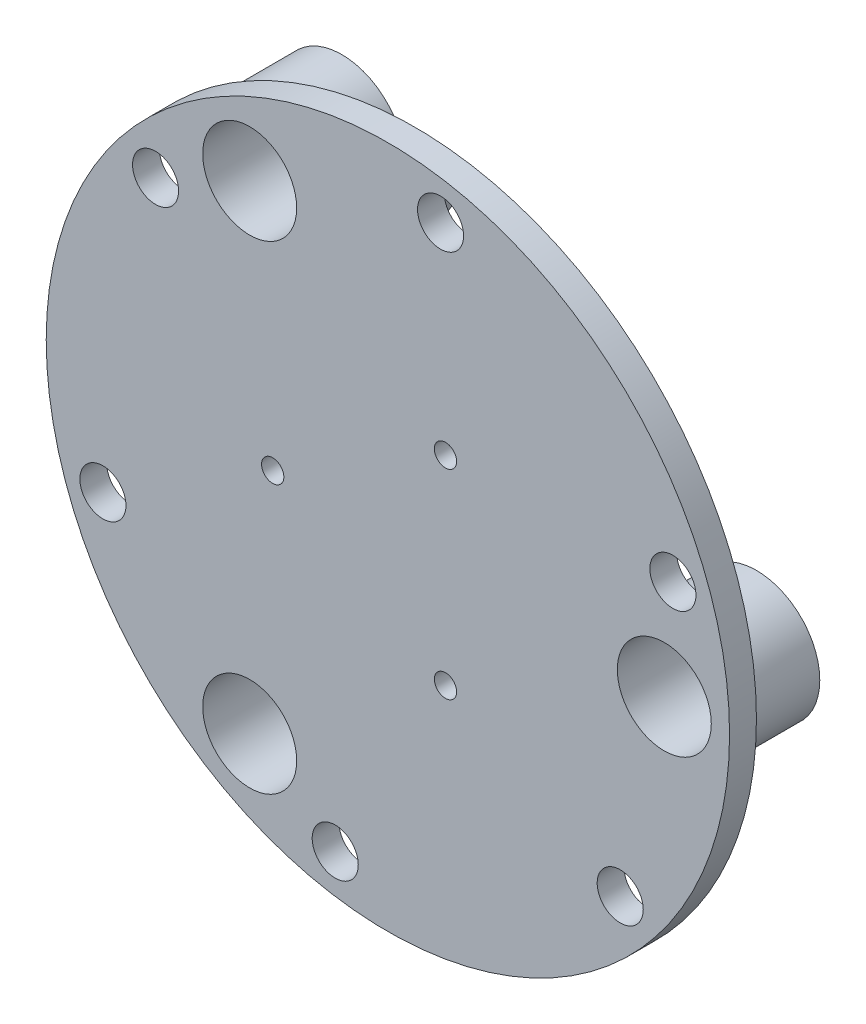
SolidWorks part; units mm, degrees
ref_plane "Front Plane" through (0, 0, 0) normal (0, 0, 1) x (1, 0, 0)
ref_plane "Top Plane" through (0, 0, 0) normal (0, 1, 0) x (1, 0, 0)
ref_plane "Right Plane" through (0, 0, 0) normal (1, 0, 0) x (0, 0, -1)
sketch "S01 - Joining centre of floating Y" plane through (0, 0, 0) normal (0, 0, 1) x (1, 0, 0)
  circle A0 centre (0, 0) radius 9
  dimension "D1" = 18
extrude "01 - Joining centre of floating Y" add sketch "S01 - Joining centre of floating Y" along normal blind 3.5 from offset 33.5
sketch "S02 - Floating spoke 1" plane through (0, 0, 0) normal (0, 0, 1) x (1, 0, 0)
  line L0 (4.65, -8.054) -> (-21.3308, -23.054)
  line L1 (-30.6308, -6.946) -> (-4.65, 8.054)
  arc A0 (-21.3308, -23.054) -> (-30.6308, -6.946) centre (-25.9808, -15) cw
  arc A1 (-4.65, 8.054) -> (4.65, -8.054) centre (0, 0) cw
  dimension "D1" = 9.3
  dimension "D2" = 9.3
  dimension "D3" = 4.65
  dimension "D4" = 4.65
  dimension "D5" = 21.3308
  dimension "D6" = 25.9808
  dimension "D7" = 30.6308
  dimension "D8" = 6.946
extrude "02 - Floating spoke 1" add sketch "S02 - Floating spoke 1" along normal blind 3.5 from offset 33.5
sketch "S03 - Floating spoke 2" plane through (0, 0, 0) normal (0, 0, 1) x (1, 0, 0)
  line L0 (4.65, 8.054) -> (30.6308, -6.946)
  line L1 (21.3308, -23.054) -> (-4.65, -8.054)
  arc A0 (30.6308, -6.946) -> (21.3308, -23.054) centre (25.9808, -15) cw
  arc A1 (-4.65, -8.054) -> (4.65, 8.054) centre (0, 0) cw
  dimension "D1" = 9.3
  dimension "D2" = 9.3
  dimension "D3" = 4.65
  dimension "D4" = 21.3308
  dimension "D5" = 25.9808
  dimension "D6" = 30.6308
  dimension "D7" = 4.65
  dimension "D8" = 6.946
extrude "03 - Floating spoke 2" add sketch "S03 - Floating spoke 2" along normal blind 3.5 from offset 33.5
sketch "S04 - Floating spoke 3" plane through (0, 0, 0) normal (0, 0, 1) x (1, 0, 0)
  line L0 (-9.3, 0) -> (-9.3, 30)
  line L1 (9.3, 30) -> (9.3, 0)
  arc A0 (-9.3, 30) -> (9.3, 30) centre (0, 30) cw
  arc A1 (9.3, 0) -> (-9.3, 0) centre (0, 0) cw
  dimension "D1" = 9.3
  dimension "D2" = 30
extrude "04 - Floating spoke 3" add sketch "S04 - Floating spoke 3" along normal blind 3.5 from offset 33.5
sketch "S05 - Moving tendon tie web 1" plane through (0, 0, 0) normal (0, 0, 1) x (1, 0, 0)
  line L0 (25.2997, -21.2631) -> (6.8189, -19.2535)
  line L1 (8.1811, -6.7273) -> (26.6618, -8.7369)
  arc A0 (6.8189, -19.2535) -> (8.1811, -6.7273) centre (7.5, -12.9904) cw
  arc A1 (26.6618, -8.7369) -> (25.2997, -21.2631) centre (25.9808, -15) cw
  dimension "D1" = 6.3
  dimension "D2" = 6.3
  dimension "D3" = 6.8189
  dimension "D4" = 7.5
  dimension "D5" = 8.1811
  dimension "D6" = 25.2997
  dimension "D7" = 25.9808
  dimension "D8" = 26.6618
  dimension "D9" = 6.7273
  dimension "D10" = 8.7369
extrude "05 - Moving tendon tie web 1" add sketch "S05 - Moving tendon tie web 1" along normal blind 3.5 from offset 33.5
sketch "S06 - Tendon anchor base 1" plane through (0, 0, 0) normal (0, 0, 1) x (1, 0, 0)
  circle A0 centre (7.5, -12.9904) radius 4.2
  dimension "D1" = 8.4
  dimension "D2" = 7.5
  dimension "D3" = 12.9904
extrude "06 - Tendon anchor base 1" add sketch "S06 - Tendon anchor base 1" along normal blind 3.7 from offset 29.8
sketch "S07 - Tendon mouth 1" plane through (0, 0, 0) normal (0, 0, 1) x (1, 0, 0)
  circle A0 centre (7.5, -12.9904) radius 3.15
  dimension "D1" = 6.3
  dimension "D2" = 7.5
  dimension "D3" = 12.9904
extrude "07 - Tendon mouth 1" add sketch "S07 - Tendon mouth 1" along normal blind 1.8 from offset 28
sketch "S08 - Moving tendon tie web 2" plane through (0, 0, 0) normal (0, 0, 1) x (1, 0, 0)
  line L0 (5.7645, 32.5417) -> (13.2645, 15.5321)
  line L1 (1.7355, 10.4487) -> (-5.7645, 27.4583)
  arc A0 (13.2645, 15.5321) -> (1.7355, 10.4487) centre (7.5, 12.9904) cw
  arc A1 (-5.7645, 27.4583) -> (5.7645, 32.5417) centre (0, 30) cw
  dimension "D1" = 6.3
  dimension "D2" = 6.3
  dimension "D3" = 1.7355
  dimension "D4" = 5.7645
  dimension "D5" = 7.5
  dimension "D6" = 13.2645
  dimension "D7" = 5.7645
  dimension "D8" = 10.4487
  dimension "D9" = 27.4583
extrude "08 - Moving tendon tie web 2" add sketch "S08 - Moving tendon tie web 2" along normal blind 3.5 from offset 33.5
sketch "S09 - Tendon anchor base 2" plane through (0, 0, 0) normal (0, 0, 1) x (1, 0, 0)
  circle A0 centre (7.5, 12.9904) radius 4.2
  dimension "D1" = 8.4
  dimension "D2" = 7.5
  dimension "D3" = 12.9904
extrude "09 - Tendon anchor base 2" add sketch "S09 - Tendon anchor base 2" along normal blind 3.7 from offset 29.8
sketch "S10 - Tendon mouth 2" plane through (0, 0, 0) normal (0, 0, 1) x (1, 0, 0)
  circle A0 centre (7.5, 12.9904) radius 3.15
  dimension "D1" = 6.3
  dimension "D2" = 7.5
  dimension "D3" = 12.9904
extrude "10 - Tendon mouth 2" add sketch "S10 - Tendon mouth 2" along normal blind 1.8 from offset 28
sketch "S11 - Moving tendon tie web 3" plane through (0, 0, 0) normal (0, 0, 1) x (1, 0, 0)
  line L0 (-31.0642, -11.2786) -> (-20.0835, 3.7214)
  line L1 (-9.9165, -3.7214) -> (-20.8973, -18.7214)
  arc A0 (-20.0835, 3.7214) -> (-9.9165, -3.7214) centre (-15, 0) cw
  arc A1 (-20.8973, -18.7214) -> (-31.0642, -11.2786) centre (-25.9808, -15) cw
  dimension "D1" = 6.3
  dimension "D2" = 6.3
  dimension "D3" = 9.9165
  dimension "D4" = 15
  dimension "D5" = 20.0835
  dimension "D6" = 20.8973
  dimension "D7" = 25.9808
  dimension "D8" = 31.0642
  dimension "D9" = 11.2786
extrude "11 - Moving tendon tie web 3" add sketch "S11 - Moving tendon tie web 3" along normal blind 3.5 from offset 33.5
sketch "S12 - Tendon anchor base 3" plane through (0, 0, 0) normal (0, 0, 1) x (1, 0, 0)
  circle A0 centre (-15, 0) radius 4.2
  dimension "D1" = 8.4
  dimension "D2" = 15
extrude "12 - Tendon anchor base 3" add sketch "S12 - Tendon anchor base 3" along normal blind 3.7 from offset 29.8
sketch "S13 - Tendon mouth 3" plane through (0, 0, 0) normal (0, 0, 1) x (1, 0, 0)
  circle A0 centre (-15, 0) radius 3.15
  dimension "D1" = 6.3
  dimension "D2" = 15
extrude "13 - Tendon mouth 3" add sketch "S13 - Tendon mouth 3" along normal blind 1.8 from offset 28
sketch "S14 - Joined drive hoop" plane through (0, 0, 0) normal (0, 0, 1) x (1, 0, 0)
  circle A0 centre (0, 0) radius 44.5
  dimension "D2" = 89
extrude "14 - Joined drive hoop" add sketch "S14 - Joined drive hoop" along normal blind 3.5 from offset 33.5
sketch "S15 - Sliding guide barrel 1" plane through (0, 0, 0) normal (0, 0, 1) x (1, 0, 0)
  circle A0 centre (36, 0) radius 8.25
  dimension "D1" = 16.5
  dimension "D2" = 36
extrude "15 - Sliding guide barrel 1" add sketch "S15 - Sliding guide barrel 1" along normal blind 12 from offset 25
sketch "S16 - Sliding guide barrel 2" plane through (0, 0, 0) normal (0, 0, 1) x (1, 0, 0)
  circle A0 centre (-18, 31.1769) radius 8.25
  dimension "D1" = 16.5
  dimension "D2" = 18
  dimension "D3" = 31.1769
extrude "16 - Sliding guide barrel 2" add sketch "S16 - Sliding guide barrel 2" along normal blind 12 from offset 25
sketch "S17 - Sliding guide barrel 3" plane through (0, 0, 0) normal (0, 0, 1) x (1, 0, 0)
  circle A0 centre (-18, -31.1769) radius 8.25
  dimension "D1" = 16.5
  dimension "D2" = 18
  dimension "D3" = 31.1769
extrude "17 - Sliding guide barrel 3" add sketch "S17 - Sliding guide barrel 3" along normal blind 12 from offset 25
sketch "S18 - Guide bushing seats" plane through (0, 0, 0) normal (0, 0, 1) x (1, 0, 0)
  circle A0 centre (36, 0) radius 6.12
  circle A1 centre (-18, 31.1769) radius 6.12
  circle A2 centre (-18, -31.1769) radius 6.12
  dimension "D1" = 12.24
  dimension "D2" = 12.24
  dimension "D3" = 12.24
  dimension "D4" = 36
  dimension "D5" = 18
  dimension "D6" = 31.1769
  dimension "D7" = 31.1769
extrude "18 - Guide bushing seats" cut sketch "S18 - Guide bushing seats" along normal blind 14 from offset 24
sketch "S19 - Through tendon tie eyes" plane through (0, 0, 0) normal (0, 0, 1) x (1, 0, 0)
  circle A0 centre (7.5, -12.9904) radius 1.45
  circle A1 centre (7.5, 12.9904) radius 1.45
  circle A2 centre (-15, 0) radius 1.45
  dimension "D1" = 2.9
  dimension "D2" = 2.9
  dimension "D3" = 2.9
  dimension "D4" = 7.5
  dimension "D5" = 15
  dimension "D6" = 12.9904
  dimension "D7" = 12.9904
extrude "19 - Through tendon tie eyes" cut sketch "S19 - Through tendon tie eyes" along normal blind 10 from offset 27.8
sketch3d "Plane points - Integral B1 fork cheek L"
  point P0 (-25.9808, -15, 28)
  point P1 (-8.5941, -10.3413, 28)
  point P2 (-25.9808, -15, 10)
ref_plane "Drilling plane - Integral B1 fork cheek L" through (2.0096, -7.5, 0) normal (-0.2588, 0.9659, 0) x (0.9659, 0.2588, 0)
sketch "S20 - Integral B1 fork cheek L" plane through (2.0096, -7.5, 0) normal (-0.2588, 0.9659, 0) x (0.9659, 0.2588, 0)
  line L0 (-35.0778, -34.5) -> (-22.8778, -34.5)
  line L1 (-22.8778, -34.5) -> (-24.0278, -28)
  line L2 (-33.9278, -28) -> (-35.0778, -34.5)
  arc A0 (-24.0278, -28) -> (-33.9278, -28) centre (-28.9778, -28) ccw
  dimension "D1" = 4.95
  dimension "D2" = 22.8778
  dimension "D3" = 28.9778
  dimension "D4" = 35.0778
  dimension "D5" = 28
  dimension "D6" = 34.5
extrude "20 - Integral B1 fork cheek L" add sketch "S20 - Integral B1 fork cheek L" along normal blind 3.6 from offset 7.2 offset against normal yes
sketch3d "Plane points - Integral B1 fork cheek R"
  point P0 (-25.9808, -15, 28)
  point P1 (-8.5941, -10.3413, 28)
  point P2 (-25.9808, -15, 10)
ref_plane "Drilling plane - Integral B1 fork cheek R" through (2.0096, -7.5, 0) normal (-0.2588, 0.9659, 0) x (0.9659, 0.2588, 0)
sketch "S21 - Integral B1 fork cheek R" plane through (2.0096, -7.5, 0) normal (-0.2588, 0.9659, 0) x (0.9659, 0.2588, 0)
  line L0 (-35.0778, -34.5) -> (-22.8778, -34.5)
  line L1 (-22.8778, -34.5) -> (-24.0278, -28)
  line L2 (-33.9278, -28) -> (-35.0778, -34.5)
  arc A0 (-24.0278, -28) -> (-33.9278, -28) centre (-28.9778, -28) ccw
  dimension "D1" = 4.95
  dimension "D2" = 22.8778
  dimension "D3" = 28.9778
  dimension "D4" = 35.0778
  dimension "D5" = 28
  dimension "D6" = 34.5
extrude "21 - Integral B1 fork cheek R" add sketch "S21 - Integral B1 fork cheek R" along normal blind 3.6 from offset 3.6
sketch3d "Plane points - B1 pivot through both cheeks"
  point P0 (-25.9808, -15, 28)
  point P1 (-8.5941, -10.3413, 28)
  point P2 (-25.9808, -15, 10)
ref_plane "Drilling plane - B1 pivot through both cheeks" through (2.0096, -7.5, 0) normal (-0.2588, 0.9659, 0) x (0.9659, 0.2588, 0)
sketch "S22 - B1 pivot through both cheeks" plane through (2.0096, -7.5, 0) normal (-0.2588, 0.9659, 0) x (0.9659, 0.2588, 0)
  circle A0 centre (-28.9778, -28) radius 1.65
  dimension "D1" = 3.3
  dimension "D2" = 28.9778
  dimension "D3" = 28
extrude "22 - B1 pivot through both cheeks" cut sketch "S22 - B1 pivot through both cheeks" along normal blind 15 from offset 7.5 offset against normal yes
sketch3d "Plane points - B1 recessed pivot screw head"
  point P0 (-25.9808, -15, 28)
  point P1 (-8.5941, -10.3413, 28)
  point P2 (-25.9808, -15, 10)
ref_plane "Drilling plane - B1 recessed pivot screw head" through (2.0096, -7.5, 0) normal (-0.2588, 0.9659, 0) x (0.9659, 0.2588, 0)
sketch "S23 - B1 recessed pivot screw head" plane through (2.0096, -7.5, 0) normal (-0.2588, 0.9659, 0) x (0.9659, 0.2588, 0)
  circle A0 centre (-28.9778, -28) radius 2.7
  dimension "D1" = 5.4
  dimension "D2" = 28.9778
  dimension "D3" = 28
extrude "23 - B1 recessed pivot screw head" cut sketch "S23 - B1 recessed pivot screw head" along normal blind 1.5 from offset 7.3 offset against normal yes
sketch3d "Plane points - Integral B2 fork cheek L"
  point P0 (25.9808, -15, 28)
  point P1 (13.2528, -2.2721, 28)
  point P2 (25.9808, -15, 10)
ref_plane "Drilling plane - Integral B2 fork cheek L" through (5.4904, 5.4904, 0) normal (-0.7071, -0.7071, 0) x (0, 0, 1)
sketch "S24 - Integral B2 fork cheek L" plane through (5.4904, 5.4904, 0) normal (-0.7071, -0.7071, 0) x (0, 0, 1)
  line L0 (34.5, -35.0778) -> (34.5, -22.8778)
  line L1 (34.5, -22.8778) -> (28, -24.0278)
  line L2 (28, -33.9278) -> (34.5, -35.0778)
  arc A0 (28, -24.0278) -> (28, -33.9278) centre (28, -28.9778) ccw
  dimension "D1" = 4.95
  dimension "D2" = 28
  dimension "D3" = 34.5
  dimension "D4" = 22.8778
  dimension "D5" = 28.9778
  dimension "D6" = 35.0778
extrude "24 - Integral B2 fork cheek L" add sketch "S24 - Integral B2 fork cheek L" along normal blind 3.6 from offset 7.2 offset against normal yes
sketch3d "Plane points - Integral B2 fork cheek R"
  point P0 (25.9808, -15, 28)
  point P1 (13.2528, -2.2721, 28)
  point P2 (25.9808, -15, 10)
ref_plane "Drilling plane - Integral B2 fork cheek R" through (5.4904, 5.4904, 0) normal (-0.7071, -0.7071, 0) x (0, 0, 1)
sketch "S25 - Integral B2 fork cheek R" plane through (5.4904, 5.4904, 0) normal (-0.7071, -0.7071, 0) x (0, 0, 1)
  line L0 (34.5, -35.0778) -> (34.5, -22.8778)
  line L1 (34.5, -22.8778) -> (28, -24.0278)
  line L2 (28, -33.9278) -> (34.5, -35.0778)
  arc A0 (28, -24.0278) -> (28, -33.9278) centre (28, -28.9778) ccw
  dimension "D1" = 4.95
  dimension "D2" = 28
  dimension "D3" = 34.5
  dimension "D4" = 22.8778
  dimension "D5" = 28.9778
  dimension "D6" = 35.0778
extrude "25 - Integral B2 fork cheek R" add sketch "S25 - Integral B2 fork cheek R" along normal blind 3.6 from offset 3.6
sketch3d "Plane points - B2 pivot through both cheeks"
  point P0 (25.9808, -15, 28)
  point P1 (13.2528, -2.2721, 28)
  point P2 (25.9808, -15, 10)
ref_plane "Drilling plane - B2 pivot through both cheeks" through (5.4904, 5.4904, 0) normal (-0.7071, -0.7071, 0) x (0, 0, 1)
sketch "S26 - B2 pivot through both cheeks" plane through (5.4904, 5.4904, 0) normal (-0.7071, -0.7071, 0) x (0, 0, 1)
  circle A0 centre (28, -28.9778) radius 2.6
  dimension "D1" = 5.2
  dimension "D2" = 28
  dimension "D3" = 28.9778
extrude "26 - B2 pivot through both cheeks" cut sketch "S26 - B2 pivot through both cheeks" along normal blind 15 from offset 7.5 offset against normal yes
sketch3d "Plane points - B2 recessed pivot screw head"
  point P0 (25.9808, -15, 28)
  point P1 (13.2528, -2.2721, 28)
  point P2 (25.9808, -15, 10)
ref_plane "Drilling plane - B2 recessed pivot screw head" through (5.4904, 5.4904, 0) normal (-0.7071, -0.7071, 0) x (0, 0, 1)
sketch "S27 - B2 recessed pivot screw head" plane through (5.4904, 5.4904, 0) normal (-0.7071, -0.7071, 0) x (0, 0, 1)
  circle A0 centre (28, -28.9778) radius 2.7
  dimension "D1" = 5.4
  dimension "D2" = 28
  dimension "D3" = 28.9778
extrude "27 - B2 recessed pivot screw head" cut sketch "S27 - B2 recessed pivot screw head" along normal blind 1.5 from offset 7.3 offset against normal yes
sketch3d "Plane points - Integral B3 fork cheek L"
  point P0 (0, 30, 28)
  point P1 (-4.6587, 12.6133, 28)
  point P2 (0, 30, 10)
ref_plane "Drilling plane - Integral B3 fork cheek L" through (-7.5, 2.0096, 0) normal (0.9659, -0.2588, 0) x (0, 0, -1)
sketch "S28 - Integral B3 fork cheek L" plane through (-7.5, 2.0096, 0) normal (0.9659, -0.2588, 0) x (0, 0, -1)
  line L0 (-34.5, 35.0778) -> (-34.5, 22.8778)
  line L1 (-34.5, 22.8778) -> (-28, 24.0278)
  line L2 (-28, 33.9278) -> (-34.5, 35.0778)
  arc A0 (-28, 24.0278) -> (-28, 33.9278) centre (-28, 28.9778) ccw
  dimension "D1" = 4.95
  dimension "D2" = 28
  dimension "D3" = 34.5
  dimension "D4" = 22.8778
  dimension "D5" = 28.9778
  dimension "D6" = 35.0778
extrude "28 - Integral B3 fork cheek L" add sketch "S28 - Integral B3 fork cheek L" along normal blind 3.6 from offset 7.2 offset against normal yes
sketch3d "Plane points - Integral B3 fork cheek R"
  point P0 (0, 30, 28)
  point P1 (-4.6587, 12.6133, 28)
  point P2 (0, 30, 10)
ref_plane "Drilling plane - Integral B3 fork cheek R" through (-7.5, 2.0096, 0) normal (0.9659, -0.2588, 0) x (0, 0, -1)
sketch "S29 - Integral B3 fork cheek R" plane through (-7.5, 2.0096, 0) normal (0.9659, -0.2588, 0) x (0, 0, -1)
  line L0 (-34.5, 35.0778) -> (-34.5, 22.8778)
  line L1 (-34.5, 22.8778) -> (-28, 24.0278)
  line L2 (-28, 33.9278) -> (-34.5, 35.0778)
  arc A0 (-28, 24.0278) -> (-28, 33.9278) centre (-28, 28.9778) ccw
  dimension "D1" = 4.95
  dimension "D2" = 28
  dimension "D3" = 34.5
  dimension "D4" = 22.8778
  dimension "D5" = 28.9778
  dimension "D6" = 35.0778
extrude "29 - Integral B3 fork cheek R" add sketch "S29 - Integral B3 fork cheek R" along normal blind 3.6 from offset 3.6
sketch3d "Plane points - B3 pivot through both cheeks"
  point P0 (0, 30, 28)
  point P1 (-4.6587, 12.6133, 28)
  point P2 (0, 30, 10)
ref_plane "Drilling plane - B3 pivot through both cheeks" through (-7.5, 2.0096, 0) normal (0.9659, -0.2588, 0) x (0, 0, -1)
sketch "S30 - B3 pivot through both cheeks" plane through (-7.5, 2.0096, 0) normal (0.9659, -0.2588, 0) x (0, 0, -1)
  circle A0 centre (-28, 28.9778) radius 2.6
  dimension "D1" = 5.2
  dimension "D2" = 28
  dimension "D3" = 28.9778
extrude "30 - B3 pivot through both cheeks" cut sketch "S30 - B3 pivot through both cheeks" along normal blind 15 from offset 7.5 offset against normal yes
sketch3d "Plane points - B3 recessed pivot screw head"
  point P0 (0, 30, 28)
  point P1 (-4.6587, 12.6133, 28)
  point P2 (0, 30, 10)
ref_plane "Drilling plane - B3 recessed pivot screw head" through (-7.5, 2.0096, 0) normal (0.9659, -0.2588, 0) x (0, 0, -1)
sketch "S31 - B3 recessed pivot screw head" plane through (-7.5, 2.0096, 0) normal (0.9659, -0.2588, 0) x (0, 0, -1)
  circle A0 centre (-28, 28.9778) radius 2.7
  dimension "D1" = 5.4
  dimension "D2" = 28
  dimension "D3" = 28.9778
extrude "31 - B3 recessed pivot screw head" cut sketch "S31 - B3 recessed pivot screw head" along normal blind 1.5 from offset 7.3 offset against normal yes
sketch "Sketch1" plane through (0.1461, -0.5453, 0) normal (-0.2588, 0.9659, 0) x (0.9659, 0.2588, 0)
  circle A0 centre (-28.9778, -28) radius 2.6
  dimension "D1" = 5.2
extrude "Cut-Extrude1" cut sketch "Sketch1" against normal blind 16 and the other way through all
other "Fork inner faces - 8.40 mm lug clearance" flip direction yes face at (-27.5604, -19.1503, 28) face at (-29.4239, -12.1956, 28) face at (30.3648, -14.2929, 28) face at (25.2737, -19.3841, 28) face at (-2.8044, 33.4432, 28) face at (4.1503, 31.5797, 28) offset 0.6 parameters "D1"=0.6
ref_plane "Guide saddle feet" through (0, 0, 25.5) normal (0, 0, 1) x (1, 0, 0)
ref_plane "Guide saddle roots" through (0, 0, 33.6) normal (0, 0, 1) x (1, 0, 0)
sketch "Barrel 1 saddle foot" plane through (0, 0, 25.5) normal (0, 0, 1) x (1, 0, 0)
  line L0 (36, -8) -> (31, -8)
  line L1 (31, -8) -> (27, -3)
  line L2 (27, 3) -> (31, 8)
  line L3 (31, 8) -> (36, 8)
  line L4 (36, 8) -> (36, 7)
  line L5 (36, -7) -> (36, -8)
  arc A0 (27, -3) -> (27, 3) centre (27, 0) cw
  arc A1 (36, 7) -> (36, -7) centre (36, 0) ccw
sketch "Barrel 1 saddle root" plane through (0, 0, 33.6) normal (0, 0, 1) x (1, 0, 0)
  line L0 (36, -8) -> (31, -8)
  line L1 (31, -8) -> (20, -4)
  line L2 (20, 4) -> (31, 8)
  line L3 (31, 8) -> (36, 8)
  line L4 (36, 8) -> (36, 7)
  line L5 (36, -7) -> (36, -8)
  arc A0 (20, -4) -> (20, 4) centre (20, 0) cw
  arc A1 (36, 7) -> (36, -7) centre (36, 0) ccw
loft "Guide barrel 1 - tapered wraparound saddle" [suppressed] add profiles "Barrel 1 saddle foot", "Barrel 1 saddle root"
sketch "Barrel 2 saddle foot" plane through (0, 0, 25.5) normal (0, 0, 1) x (1, 0, 0)
  line L0 (-11.0718, 35.1769) -> (-8.5718, 30.8468)
  line L1 (-8.5718, 30.8468) -> (-10.9019, 24.8827)
  line L2 (-16.0981, 21.8827) -> (-22.4282, 22.8468)
  line L3 (-22.4282, 22.8468) -> (-24.9282, 27.1769)
  line L4 (-24.9282, 27.1769) -> (-24.0622, 27.6769)
  line L5 (-11.9378, 34.6769) -> (-11.0718, 35.1769)
  arc A0 (-10.9019, 24.8827) -> (-16.0981, 21.8827) centre (-13.5, 23.3827) cw
  arc A1 (-24.0622, 27.6769) -> (-11.9378, 34.6769) centre (-18, 31.1769) ccw
sketch "Barrel 2 saddle root" plane through (0, 0, 33.6) normal (0, 0, 1) x (1, 0, 0)
  line L0 (-11.0718, 35.1769) -> (-8.5718, 30.8468)
  line L1 (-8.5718, 30.8468) -> (-6.5359, 19.3205)
  line L2 (-13.4641, 15.3205) -> (-22.4282, 22.8468)
  line L3 (-22.4282, 22.8468) -> (-24.9282, 27.1769)
  line L4 (-24.9282, 27.1769) -> (-24.0622, 27.6769)
  line L5 (-11.9378, 34.6769) -> (-11.0718, 35.1769)
  arc A0 (-6.5359, 19.3205) -> (-13.4641, 15.3205) centre (-10, 17.3205) cw
  arc A1 (-24.0622, 27.6769) -> (-11.9378, 34.6769) centre (-18, 31.1769) ccw
loft "Guide barrel 2 - tapered wraparound saddle" [suppressed] add profiles "Barrel 2 saddle foot", "Barrel 2 saddle root"
sketch "Barrel 3 saddle foot" plane through (0, 0, 25.5) normal (0, 0, 1) x (1, 0, 0)
  line L0 (-24.9282, -27.1769) -> (-22.4282, -22.8468)
  line L1 (-22.4282, -22.8468) -> (-16.0981, -21.8827)
  line L2 (-10.9019, -24.8827) -> (-8.5718, -30.8468)
  line L3 (-8.5718, -30.8468) -> (-11.0718, -35.1769)
  line L4 (-11.0718, -35.1769) -> (-11.9378, -34.6769)
  line L5 (-24.0622, -27.6769) -> (-24.9282, -27.1769)
  arc A0 (-16.0981, -21.8827) -> (-10.9019, -24.8827) centre (-13.5, -23.3827) cw
  arc A1 (-11.9378, -34.6769) -> (-24.0622, -27.6769) centre (-18, -31.1769) ccw
sketch "Barrel 3 saddle root" plane through (0, 0, 33.6) normal (0, 0, 1) x (1, 0, 0)
  line L0 (-24.9282, -27.1769) -> (-22.4282, -22.8468)
  line L1 (-22.4282, -22.8468) -> (-13.4641, -15.3205)
  line L2 (-6.5359, -19.3205) -> (-8.5718, -30.8468)
  line L3 (-8.5718, -30.8468) -> (-11.0718, -35.1769)
  line L4 (-11.0718, -35.1769) -> (-11.9378, -34.6769)
  line L5 (-24.0622, -27.6769) -> (-24.9282, -27.1769)
  arc A0 (-13.4641, -15.3205) -> (-6.5359, -19.3205) centre (-10, -17.3205) cw
  arc A1 (-11.9378, -34.6769) -> (-24.0622, -27.6769) centre (-18, -31.1769) ccw
loft "Guide barrel 3 - tapered wraparound saddle" [suppressed] add profiles "Barrel 3 saddle foot", "Barrel 3 saddle root"
sketch "Tangent R6.5 transitions at guide stations" plane through (0, 0, 0) normal (0, 0, 1) x (1, 0, 0)
  line L0 (39.3501, -7.5392) -> (35.4, -7.5)
  line L1 (35.4, -7.5) -> (35.8006, -11.4924)
  line L2 (39.3501, 7.5392) -> (35.4, 7.5)
  line L3 (35.4, 7.5) -> (35.8006, 11.4924)
  line L4 (-13.1459, 37.8478) -> (-11.2048, 34.4073)
  line L5 (-11.2048, 34.4073) -> (-7.9476, 36.7505)
  line L6 (-26.2042, 30.3086) -> (-24.1952, 26.9073)
  line L7 (-24.1952, 26.9073) -> (-27.853, 25.258)
  line L8 (-26.2042, -30.3086) -> (-24.1952, -26.9073)
  line L9 (-24.1952, -26.9073) -> (-27.853, -25.258)
  line L10 (-13.1459, -37.8478) -> (-11.2048, -34.4073)
  line L11 (-11.2048, -34.4073) -> (-7.9476, -36.7505)
  arc A0 (35.8006, -11.4924) -> (39.3501, -7.5392) centre (41.9895, -13.4792) cw
  arc A1 (35.8006, 11.4924) -> (39.3501, 7.5392) centre (41.9895, 13.4792) ccw
  arc A2 (-7.9476, 36.7505) -> (-13.1459, 37.8478) centre (-9.3215, 43.1036) cw
  arc A3 (-27.853, 25.258) -> (-26.2042, 30.3086) centre (-32.6681, 29.6244) ccw
  arc A4 (-27.853, -25.258) -> (-26.2042, -30.3086) centre (-32.6681, -29.6244) cw
  arc A5 (-7.9476, -36.7505) -> (-13.1459, -37.8478) centre (-9.3215, -43.1036) ccw
extrude "Continuous deck rim around bearing housings" [suppressed] add sketch "Tangent R6.5 transitions at guide stations" along normal blind 3.5 from offset 33.5
sketch3d "Guide 1 clockwise anchor section"
  line L0 (11.4747, -15.0801, 33.56) -> (8.53, -8.6195, 33.56)
  line L1 (8.53, -8.6195, 33.56) -> (8.9447, -9.5295, 32.56)
  line L2 (8.9447, -9.5295, 32.56) -> (9.1313, -9.939, 30.55)
  line L3 (9.1313, -9.939, 30.55) -> (9.318, -10.3484, 30.1)
  line L4 (9.318, -10.3484, 30.1) -> (10.6867, -13.3512, 30.1)
  line L5 (10.6867, -13.3512, 30.1) -> (10.8733, -13.7607, 30.55)
  line L6 (10.8733, -13.7607, 30.55) -> (11.0599, -14.1702, 32.56)
  line L7 (11.0599, -14.1702, 32.56) -> (11.4747, -15.0801, 33.56)
sketch3d "Guide 1 clockwise web section"
  line L0 (19.1463, -10.8141, 33.56) -> (16.7822, -5.6274, 33.56)
  line L1 (16.7822, -5.6274, 33.56) -> (17.197, -6.5374, 32.56)
  line L2 (17.197, -6.5374, 32.56) -> (17.3836, -6.9468, 30.45)
  line L3 (17.3836, -6.9468, 30.45) -> (17.5702, -7.3563, 30)
  line L4 (17.5702, -7.3563, 30) -> (18.3583, -9.0852, 30)
  line L5 (18.3583, -9.0852, 30) -> (18.5449, -9.4947, 30.45)
  line L6 (18.5449, -9.4947, 30.45) -> (18.7315, -9.9041, 32.56)
  line L7 (18.7315, -9.9041, 32.56) -> (19.1463, -10.8141, 33.56)
sketch3d "Guide 1 clockwise haunch section"
  line L0 (26.5692, -7.7604, 33.56) -> (23.9563, -2.0278, 33.56)
  line L1 (23.9563, -2.0278, 33.56) -> (24.3711, -2.9377, 32.56)
  line L2 (24.3711, -2.9377, 32.56) -> (24.5577, -3.3472, 27.45)
  line L3 (24.5577, -3.3472, 27.45) -> (24.7443, -3.7566, 27)
  line L4 (24.7443, -3.7566, 27) -> (25.7812, -6.0315, 27)
  line L5 (25.7812, -6.0315, 27) -> (25.9678, -6.441, 27.45)
  line L6 (25.9678, -6.441, 27.45) -> (26.1545, -6.8504, 32.56)
  line L7 (26.1545, -6.8504, 32.56) -> (26.5692, -7.7604, 33.56)
sketch3d "Guide 1 clockwise housing section"
  line L0 (31.8441, -6.6748, 33.56) -> (28.2358, 1.2416, 33.56)
  line L1 (28.2358, 1.2416, 33.56) -> (28.6505, 0.3317, 32.56)
  line L2 (28.6505, 0.3317, 32.56) -> (28.8371, -0.0778, 25.9)
  line L3 (28.8371, -0.0778, 25.9) -> (29.0238, -0.4873, 25.45)
  line L4 (29.0238, -0.4873, 25.45) -> (31.0561, -4.946, 25.45)
  line L5 (31.0561, -4.946, 25.45) -> (31.2427, -5.3554, 25.9)
  line L6 (31.2427, -5.3554, 25.9) -> (31.4293, -5.7649, 32.56)
  line L7 (31.4293, -5.7649, 32.56) -> (31.8441, -6.6748, 33.56)
loft "Guide 1 clockwise bearing-to-anchor rib" [suppressed] add profiles "Guide 1 clockwise anchor section", "Guide 1 clockwise web section", "Guide 1 clockwise haunch section", "Guide 1 clockwise housing section"
sketch3d "Guide 1 counterclockwise anchor section"
  line L0 (8.53, 8.6195, 33.56) -> (11.4747, 15.0801, 33.56)
  line L1 (11.4747, 15.0801, 33.56) -> (11.0599, 14.1702, 32.56)
  line L2 (11.0599, 14.1702, 32.56) -> (10.8733, 13.7607, 30.55)
  line L3 (10.8733, 13.7607, 30.55) -> (10.6867, 13.3512, 30.1)
  line L4 (10.6867, 13.3512, 30.1) -> (9.318, 10.3484, 30.1)
  line L5 (9.318, 10.3484, 30.1) -> (9.1313, 9.939, 30.55)
  line L6 (9.1313, 9.939, 30.55) -> (8.9447, 9.5295, 32.56)
  line L7 (8.9447, 9.5295, 32.56) -> (8.53, 8.6195, 33.56)
sketch3d "Guide 1 counterclockwise web section"
  line L0 (16.7822, 5.6274, 33.56) -> (19.1463, 10.8141, 33.56)
  line L1 (19.1463, 10.8141, 33.56) -> (18.7315, 9.9041, 32.56)
  line L2 (18.7315, 9.9041, 32.56) -> (18.5449, 9.4947, 30.45)
  line L3 (18.5449, 9.4947, 30.45) -> (18.3583, 9.0852, 30)
  line L4 (18.3583, 9.0852, 30) -> (17.5702, 7.3563, 30)
  line L5 (17.5702, 7.3563, 30) -> (17.3836, 6.9468, 30.45)
  line L6 (17.3836, 6.9468, 30.45) -> (17.197, 6.5374, 32.56)
  line L7 (17.197, 6.5374, 32.56) -> (16.7822, 5.6274, 33.56)
sketch3d "Guide 1 counterclockwise haunch section"
  line L0 (23.9563, 2.0278, 33.56) -> (26.5692, 7.7604, 33.56)
  line L1 (26.5692, 7.7604, 33.56) -> (26.1545, 6.8504, 32.56)
  line L2 (26.1545, 6.8504, 32.56) -> (25.9678, 6.441, 27.45)
  line L3 (25.9678, 6.441, 27.45) -> (25.7812, 6.0315, 27)
  line L4 (25.7812, 6.0315, 27) -> (24.7443, 3.7566, 27)
  line L5 (24.7443, 3.7566, 27) -> (24.5577, 3.3472, 27.45)
  line L6 (24.5577, 3.3472, 27.45) -> (24.3711, 2.9377, 32.56)
  line L7 (24.3711, 2.9377, 32.56) -> (23.9563, 2.0278, 33.56)
sketch3d "Guide 1 counterclockwise housing section"
  line L0 (28.2358, -1.2416, 33.56) -> (31.8441, 6.6748, 33.56)
  line L1 (31.8441, 6.6748, 33.56) -> (31.4293, 5.7649, 32.56)
  line L2 (31.4293, 5.7649, 32.56) -> (31.2427, 5.3554, 25.9)
  line L3 (31.2427, 5.3554, 25.9) -> (31.0561, 4.946, 25.45)
  line L4 (31.0561, 4.946, 25.45) -> (29.0238, 0.4873, 25.45)
  line L5 (29.0238, 0.4873, 25.45) -> (28.8371, 0.0778, 25.9)
  line L6 (28.8371, 0.0778, 25.9) -> (28.6505, -0.3317, 32.56)
  line L7 (28.6505, -0.3317, 32.56) -> (28.2358, -1.2416, 33.56)
loft "Guide 1 counterclockwise bearing-to-anchor rib" [suppressed] add profiles "Guide 1 counterclockwise anchor section", "Guide 1 counterclockwise web section", "Guide 1 counterclockwise haunch section", "Guide 1 counterclockwise housing section"
sketch3d "Guide 2 clockwise anchor section"
  line L0 (7.3224, 17.4774, 33.56) -> (3.1998, 11.6969, 33.56)
  line L1 (3.1998, 11.6969, 33.56) -> (3.7804, 12.5111, 32.56)
  line L2 (3.7804, 12.5111, 32.56) -> (4.0417, 12.8775, 30.55)
  line L3 (4.0417, 12.8775, 30.55) -> (4.303, 13.2438, 30.1)
  line L4 (4.303, 13.2438, 30.1) -> (6.2192, 15.9305, 30.1)
  line L5 (6.2192, 15.9305, 30.1) -> (6.4804, 16.2969, 30.55)
  line L6 (6.4804, 16.2969, 30.55) -> (6.7417, 16.6633, 32.56)
  line L7 (6.7417, 16.6633, 32.56) -> (7.3224, 17.4774, 33.56)
sketch3d "Guide 2 clockwise web section"
  line L0 (-0.2079, 21.9882, 33.56) -> (-3.5176, 17.3475, 33.56)
  line L1 (-3.5176, 17.3475, 33.56) -> (-2.937, 18.1617, 32.56)
  line L2 (-2.937, 18.1617, 32.56) -> (-2.6757, 18.5281, 30.45)
  line L3 (-2.6757, 18.5281, 30.45) -> (-2.4144, 18.8944, 30)
  line L4 (-2.4144, 18.8944, 30) -> (-1.3111, 20.4413, 30)
  line L5 (-1.3111, 20.4413, 30) -> (-1.0498, 20.8077, 30.45)
  line L6 (-1.0498, 20.8077, 30.45) -> (-0.7885, 21.1741, 32.56)
  line L7 (-0.7885, 21.1741, 32.56) -> (-0.2079, 21.9882, 33.56)
sketch3d "Guide 2 clockwise haunch section"
  line L0 (-6.564, 26.8898, 33.56) -> (-10.2221, 21.7606, 33.56)
  line L1 (-10.2221, 21.7606, 33.56) -> (-9.6414, 22.5748, 32.56)
  line L2 (-9.6414, 22.5748, 32.56) -> (-9.3801, 22.9412, 27.45)
  line L3 (-9.3801, 22.9412, 27.45) -> (-9.1188, 23.3075, 27)
  line L4 (-9.1188, 23.3075, 27) -> (-7.6672, 25.3429, 27)
  line L5 (-7.6672, 25.3429, 27) -> (-7.4059, 25.7093, 27.45)
  line L6 (-7.4059, 25.7093, 27.45) -> (-7.1446, 26.0757, 32.56)
  line L7 (-7.1446, 26.0757, 32.56) -> (-6.564, 26.8898, 33.56)
sketch3d "Guide 2 clockwise housing section"
  line L0 (-10.1415, 30.9152, 33.56) -> (-15.1931, 23.8321, 33.56)
  line L1 (-15.1931, 23.8321, 33.56) -> (-14.6125, 24.6462, 32.56)
  line L2 (-14.6125, 24.6462, 32.56) -> (-14.3512, 25.0126, 25.9)
  line L3 (-14.3512, 25.0126, 25.9) -> (-14.0899, 25.379, 25.45)
  line L4 (-14.0899, 25.379, 25.45) -> (-11.2447, 29.3683, 25.45)
  line L5 (-11.2447, 29.3683, 25.45) -> (-10.9834, 29.7347, 25.9)
  line L6 (-10.9834, 29.7347, 25.9) -> (-10.7221, 30.1011, 32.56)
  line L7 (-10.7221, 30.1011, 32.56) -> (-10.1415, 30.9152, 33.56)
loft "Guide 2 clockwise bearing-to-anchor rib" [suppressed] add profiles "Guide 2 clockwise anchor section", "Guide 2 clockwise web section", "Guide 2 clockwise haunch section", "Guide 2 clockwise housing section"
sketch3d "Guide 2 counterclockwise anchor section"
  line L0 (-11.7297, 3.0774, 33.56) -> (-18.7971, 2.3973, 33.56)
  line L1 (-18.7971, 2.3973, 33.56) -> (-17.8017, 2.4931, 32.56)
  line L2 (-17.8017, 2.4931, 32.56) -> (-17.3537, 2.5362, 30.55)
  line L3 (-17.3537, 2.5362, 30.55) -> (-16.9058, 2.5793, 30.1)
  line L4 (-16.9058, 2.5793, 30.1) -> (-13.621, 2.8954, 30.1)
  line L5 (-13.621, 2.8954, 30.1) -> (-13.1731, 2.9385, 30.55)
  line L6 (-13.1731, 2.9385, 30.55) -> (-12.7251, 2.9816, 32.56)
  line L7 (-12.7251, 2.9816, 32.56) -> (-11.7297, 3.0774, 33.56)
sketch3d "Guide 2 counterclockwise web section"
  line L0 (-13.2646, 11.7201, 33.56) -> (-18.9384, 11.1741, 33.56)
  line L1 (-18.9384, 11.1741, 33.56) -> (-17.943, 11.2699, 32.56)
  line L2 (-17.943, 11.2699, 32.56) -> (-17.4951, 11.313, 30.45)
  line L3 (-17.4951, 11.313, 30.45) -> (-17.0471, 11.3561, 30)
  line L4 (-17.0471, 11.3561, 30) -> (-15.1559, 11.5381, 30)
  line L5 (-15.1559, 11.5381, 30) -> (-14.7079, 11.5812, 30.45)
  line L6 (-14.7079, 11.5812, 30.45) -> (-14.26, 11.6243, 32.56)
  line L7 (-14.26, 11.6243, 32.56) -> (-13.2646, 11.7201, 33.56)
sketch3d "Guide 2 counterclockwise haunch section"
  line L0 (-13.7342, 19.7329, 33.56) -> (-20.0053, 19.1295, 33.56)
  line L1 (-20.0053, 19.1295, 33.56) -> (-19.0099, 19.2252, 32.56)
  line L2 (-19.0099, 19.2252, 32.56) -> (-18.5619, 19.2683, 27.45)
  line L3 (-18.5619, 19.2683, 27.45) -> (-18.114, 19.3114, 27)
  line L4 (-18.114, 19.3114, 27) -> (-15.6255, 19.5509, 27)
  line L5 (-15.6255, 19.5509, 27) -> (-15.1776, 19.594, 27.45)
  line L6 (-15.1776, 19.594, 27.45) -> (-14.7297, 19.6371, 32.56)
  line L7 (-14.7297, 19.6371, 32.56) -> (-13.7342, 19.7329, 33.56)
sketch3d "Guide 2 counterclockwise housing section"
  line L0 (-13.0426, 25.0737, 33.56) -> (-21.7026, 24.2404, 33.56)
  line L1 (-21.7026, 24.2404, 33.56) -> (-20.7072, 24.3362, 32.56)
  line L2 (-20.7072, 24.3362, 32.56) -> (-20.2593, 24.3793, 25.9)
  line L3 (-20.2593, 24.3793, 25.9) -> (-19.8114, 24.4224, 25.45)
  line L4 (-19.8114, 24.4224, 25.45) -> (-14.9339, 24.8917, 25.45)
  line L5 (-14.9339, 24.8917, 25.45) -> (-14.486, 24.9348, 25.9)
  line L6 (-14.486, 24.9348, 25.9) -> (-14.038, 24.9779, 32.56)
  line L7 (-14.038, 24.9779, 32.56) -> (-13.0426, 25.0737, 33.56)
loft "Guide 2 counterclockwise bearing-to-anchor rib" [suppressed] add profiles "Guide 2 counterclockwise anchor section", "Guide 2 counterclockwise web section", "Guide 2 counterclockwise haunch section", "Guide 2 counterclockwise housing section"
sketch3d "Guide 3 clockwise anchor section"
  line L0 (-18.7971, -2.3973, 33.56) -> (-11.7297, -3.0774, 33.56)
  line L1 (-11.7297, -3.0774, 33.56) -> (-12.7251, -2.9816, 32.56)
  line L2 (-12.7251, -2.9816, 32.56) -> (-13.1731, -2.9385, 30.55)
  line L3 (-13.1731, -2.9385, 30.55) -> (-13.621, -2.8954, 30.1)
  line L4 (-13.621, -2.8954, 30.1) -> (-16.9058, -2.5793, 30.1)
  line L5 (-16.9058, -2.5793, 30.1) -> (-17.3537, -2.5362, 30.55)
  line L6 (-17.3537, -2.5362, 30.55) -> (-17.8017, -2.4931, 32.56)
  line L7 (-17.8017, -2.4931, 32.56) -> (-18.7971, -2.3973, 33.56)
sketch3d "Guide 3 clockwise web section"
  line L0 (-18.9384, -11.1741, 33.56) -> (-13.2646, -11.7201, 33.56)
  line L1 (-13.2646, -11.7201, 33.56) -> (-14.26, -11.6243, 32.56)
  line L2 (-14.26, -11.6243, 32.56) -> (-14.7079, -11.5812, 30.45)
  line L3 (-14.7079, -11.5812, 30.45) -> (-15.1559, -11.5381, 30)
  line L4 (-15.1559, -11.5381, 30) -> (-17.0471, -11.3561, 30)
  line L5 (-17.0471, -11.3561, 30) -> (-17.4951, -11.313, 30.45)
  line L6 (-17.4951, -11.313, 30.45) -> (-17.943, -11.2699, 32.56)
  line L7 (-17.943, -11.2699, 32.56) -> (-18.9384, -11.1741, 33.56)
sketch3d "Guide 3 clockwise haunch section"
  line L0 (-20.0053, -19.1295, 33.56) -> (-13.7342, -19.7329, 33.56)
  line L1 (-13.7342, -19.7329, 33.56) -> (-14.7297, -19.6371, 32.56)
  line L2 (-14.7297, -19.6371, 32.56) -> (-15.1776, -19.594, 27.45)
  line L3 (-15.1776, -19.594, 27.45) -> (-15.6255, -19.5509, 27)
  line L4 (-15.6255, -19.5509, 27) -> (-18.114, -19.3114, 27)
  line L5 (-18.114, -19.3114, 27) -> (-18.5619, -19.2683, 27.45)
  line L6 (-18.5619, -19.2683, 27.45) -> (-19.0099, -19.2252, 32.56)
  line L7 (-19.0099, -19.2252, 32.56) -> (-20.0053, -19.1295, 33.56)
sketch3d "Guide 3 clockwise housing section"
  line L0 (-21.7026, -24.2404, 33.56) -> (-13.0426, -25.0737, 33.56)
  line L1 (-13.0426, -25.0737, 33.56) -> (-14.038, -24.9779, 32.56)
  line L2 (-14.038, -24.9779, 32.56) -> (-14.486, -24.9348, 25.9)
  line L3 (-14.486, -24.9348, 25.9) -> (-14.9339, -24.8917, 25.45)
  line L4 (-14.9339, -24.8917, 25.45) -> (-19.8114, -24.4224, 25.45)
  line L5 (-19.8114, -24.4224, 25.45) -> (-20.2593, -24.3793, 25.9)
  line L6 (-20.2593, -24.3793, 25.9) -> (-20.7072, -24.3362, 32.56)
  line L7 (-20.7072, -24.3362, 32.56) -> (-21.7026, -24.2404, 33.56)
loft "Guide 3 clockwise bearing-to-anchor rib" [suppressed] add profiles "Guide 3 clockwise anchor section", "Guide 3 clockwise web section", "Guide 3 clockwise haunch section", "Guide 3 clockwise housing section"
sketch3d "Guide 3 counterclockwise anchor section"
  line L0 (3.1998, -11.6969, 33.56) -> (7.3224, -17.4774, 33.56)
  line L1 (7.3224, -17.4774, 33.56) -> (6.7417, -16.6633, 32.56)
  line L2 (6.7417, -16.6633, 32.56) -> (6.4804, -16.2969, 30.55)
  line L3 (6.4804, -16.2969, 30.55) -> (6.2192, -15.9305, 30.1)
  line L4 (6.2192, -15.9305, 30.1) -> (4.303, -13.2438, 30.1)
  line L5 (4.303, -13.2438, 30.1) -> (4.0417, -12.8775, 30.55)
  line L6 (4.0417, -12.8775, 30.55) -> (3.7804, -12.5111, 32.56)
  line L7 (3.7804, -12.5111, 32.56) -> (3.1998, -11.6969, 33.56)
sketch3d "Guide 3 counterclockwise web section"
  line L0 (-3.5176, -17.3475, 33.56) -> (-0.2079, -21.9882, 33.56)
  line L1 (-0.2079, -21.9882, 33.56) -> (-0.7885, -21.1741, 32.56)
  line L2 (-0.7885, -21.1741, 32.56) -> (-1.0498, -20.8077, 30.45)
  line L3 (-1.0498, -20.8077, 30.45) -> (-1.3111, -20.4413, 30)
  line L4 (-1.3111, -20.4413, 30) -> (-2.4144, -18.8944, 30)
  line L5 (-2.4144, -18.8944, 30) -> (-2.6757, -18.5281, 30.45)
  line L6 (-2.6757, -18.5281, 30.45) -> (-2.937, -18.1617, 32.56)
  line L7 (-2.937, -18.1617, 32.56) -> (-3.5176, -17.3475, 33.56)
sketch3d "Guide 3 counterclockwise haunch section"
  line L0 (-10.2221, -21.7606, 33.56) -> (-6.564, -26.8898, 33.56)
  line L1 (-6.564, -26.8898, 33.56) -> (-7.1446, -26.0757, 32.56)
  line L2 (-7.1446, -26.0757, 32.56) -> (-7.4059, -25.7093, 27.45)
  line L3 (-7.4059, -25.7093, 27.45) -> (-7.6672, -25.3429, 27)
  line L4 (-7.6672, -25.3429, 27) -> (-9.1188, -23.3075, 27)
  line L5 (-9.1188, -23.3075, 27) -> (-9.3801, -22.9412, 27.45)
  line L6 (-9.3801, -22.9412, 27.45) -> (-9.6414, -22.5748, 32.56)
  line L7 (-9.6414, -22.5748, 32.56) -> (-10.2221, -21.7606, 33.56)
sketch3d "Guide 3 counterclockwise housing section"
  line L0 (-15.1931, -23.8321, 33.56) -> (-10.1415, -30.9152, 33.56)
  line L1 (-10.1415, -30.9152, 33.56) -> (-10.7221, -30.1011, 32.56)
  line L2 (-10.7221, -30.1011, 32.56) -> (-10.9834, -29.7347, 25.9)
  line L3 (-10.9834, -29.7347, 25.9) -> (-11.2447, -29.3683, 25.45)
  line L4 (-11.2447, -29.3683, 25.45) -> (-14.0899, -25.379, 25.45)
  line L5 (-14.0899, -25.379, 25.45) -> (-14.3512, -25.0126, 25.9)
  line L6 (-14.3512, -25.0126, 25.9) -> (-14.6125, -24.6462, 32.56)
  line L7 (-14.6125, -24.6462, 32.56) -> (-15.1931, -23.8321, 33.56)
loft "Guide 3 counterclockwise bearing-to-anchor rib" [suppressed] add profiles "Guide 3 counterclockwise anchor section", "Guide 3 counterclockwise web section", "Guide 3 counterclockwise haunch section", "Guide 3 counterclockwise housing section"
sketch "Six radiused carrier openings" plane through (0, 0, 0) normal (0, 0, 1) x (1, 0, 0)
  line L0 (13.6035, -5.5701) -> (22.1253, -1.8315)
  line L1 (22.1253, 1.8315) -> (13.6035, 5.5701)
  line L2 (10.8, 3.7386) -> (10.8, -3.7386)
  line L3 (26.2356, 15.0695) -> (25.2894, 19.0749)
  line L4 (23.9074, 20.9252) -> (14.2389, 26.4581)
  line L5 (10.0422, 23.0395) -> (10.902, 20.4109)
  line L6 (11.9821, 18.946) -> (21.737, 12.0363)
  line L7 (-1.9779, 14.566) -> (-9.4765, 20.0768)
  line L8 (-12.6488, 18.2453) -> (-11.6256, 8.9959)
  line L9 (-8.6377, 7.4838) -> (-2.1623, 11.2224)
  line L10 (-26.1683, 15.1859) -> (-29.164, 12.3638)
  line L11 (-30.0755, 10.2418) -> (-30.0328, -0.8978)
  line L12 (-24.9739, -2.8229) -> (-23.1274, -0.764)
  line L13 (-22.3988, 0.9038) -> (-21.2922, 12.8066)
  line L14 (-11.6256, -8.9959) -> (-12.6488, -18.2453)
  line L15 (-9.4765, -20.0768) -> (-1.9779, -14.566)
  line L16 (-2.1623, -11.2224) -> (-8.6377, -7.4838)
  line L17 (-0.0672, -30.2554) -> (3.8747, -31.4387)
  line L18 (6.1681, -31.1671) -> (15.7939, -25.5603)
  line L19 (14.9317, -20.2166) -> (12.2253, -19.6469)
  line L20 (10.4167, -19.8498) -> (-0.4447, -24.8429)
  arc A0 (10.8, -3.7386) -> (13.6035, -5.5701) centre (12.8, -3.7386) ccw
  arc A1 (22.1253, -1.8315) -> (22.1253, 1.8315) centre (21.3218, 0) ccw
  arc A2 (13.6035, 5.5701) -> (10.8, 3.7386) centre (12.8, 3.7386) ccw
  arc A3 (21.737, 12.0363) -> (26.2356, 15.0695) centre (23.4132, 14.4028) ccw
  arc A4 (25.2894, 19.0749) -> (23.9074, 20.9252) centre (22.4671, 18.4082) ccw
  arc A5 (14.2389, 26.4581) -> (10.0422, 23.0395) centre (12.7985, 23.9411) ccw
  arc A6 (10.902, 20.4109) -> (11.9821, 18.946) centre (13.6583, 21.3125) ccw
  arc A7 (-2.1623, 11.2224) -> (-1.9779, 14.566) centre (-3.1623, 12.9544) ccw
  arc A8 (-9.4765, 20.0768) -> (-12.6488, 18.2453) centre (-10.6609, 18.4652) ccw
  arc A9 (-11.6256, 8.9959) -> (-8.6377, 7.4838) centre (-9.6377, 9.2158) ccw
  arc A10 (-21.2922, 12.8066) -> (-26.1683, 15.1859) centre (-24.1798, 13.0751) ccw
  arc A11 (-29.164, 12.3638) -> (-30.0755, 10.2418) centre (-27.1755, 10.2529) ccw
  arc A12 (-30.0328, -0.8978) -> (-24.9739, -2.8229) centre (-27.1328, -0.8867) ccw
  arc A13 (-23.1274, -0.764) -> (-22.3988, 0.9038) centre (-25.2863, 1.1722) ccw
  arc A14 (-8.6377, -7.4838) -> (-11.6256, -8.9959) centre (-9.6377, -9.2158) ccw
  arc A15 (-12.6488, -18.2453) -> (-9.4765, -20.0768) centre (-10.6609, -18.4652) ccw
  arc A16 (-1.9779, -14.566) -> (-2.1623, -11.2224) centre (-3.1623, -12.9544) ccw
  arc A17 (-0.4447, -24.8429) -> (-0.0672, -30.2554) centre (0.7666, -27.4778) ccw
  arc A18 (3.8747, -31.4387) -> (6.1681, -31.1671) centre (4.7084, -28.6612) ccw
  arc A19 (15.7939, -25.5603) -> (14.9317, -20.2166) centre (14.3343, -23.0544) ccw
  arc A20 (12.2253, -19.6469) -> (10.4167, -19.8498) centre (11.628, -22.4847) ccw
extrude "Open deck between guide, tendon and fork stations" [suppressed] cut sketch "Six radiused carrier openings" against normal blind 3.65 from offset 37.05
sketch3d "Guide 1 right trapezoidal rib - tendon end"
  line L0 (10.7863, -13.6904, 33.55) -> (9.1273, -10.0507, 33.55)
  line L1 (9.1273, -10.0507, 33.55) -> (9.2955, -10.4197, 31.25)
  line L2 (9.2955, -10.4197, 31.25) -> (10.6181, -13.3214, 31.25)
  line L3 (10.6181, -13.3214, 31.25) -> (10.7863, -13.6904, 33.55)
sketch3d "Guide 1 right trapezoidal rib - guide end"
  line L0 (31.1932, -5.4879, 33.55) -> (28.7047, -0.0283, 33.55)
  line L1 (28.7047, -0.0283, 33.55) -> (29.1618, -1.0311, 27.3)
  line L2 (29.1618, -1.0311, 27.3) -> (30.7361, -4.4851, 27.3)
  line L3 (30.7361, -4.4851, 27.3) -> (31.1932, -5.4879, 33.55)
loft "Guide 1 right trapezoidal rib" [suppressed] add profiles "Guide 1 right trapezoidal rib - tendon end", "Guide 1 right trapezoidal rib - guide end"
sketch3d "Guide 1 left trapezoidal rib - tendon end"
  line L0 (9.1273, 10.0507, 33.55) -> (10.7863, 13.6904, 33.55)
  line L1 (10.7863, 13.6904, 33.55) -> (10.6181, 13.3214, 31.25)
  line L2 (10.6181, 13.3214, 31.25) -> (9.2955, 10.4197, 31.25)
  line L3 (9.2955, 10.4197, 31.25) -> (9.1273, 10.0507, 33.55)
sketch3d "Guide 1 left trapezoidal rib - guide end"
  line L0 (28.7047, 0.0283, 33.55) -> (31.1932, 5.4879, 33.55)
  line L1 (31.1932, 5.4879, 33.55) -> (30.7361, 4.4851, 27.3)
  line L2 (30.7361, 4.4851, 27.3) -> (29.1618, 1.0311, 27.3)
  line L3 (29.1618, 1.0311, 27.3) -> (28.7047, 0.0283, 33.55)
loft "Guide 1 left trapezoidal rib" [suppressed] add profiles "Guide 1 left trapezoidal rib - tendon end", "Guide 1 left trapezoidal rib - guide end"
sketch3d "Guide 2 right trapezoidal rib - tendon end"
  line L0 (6.4631, 16.1864, 33.55) -> (4.1405, 12.9298, 33.55)
  line L1 (4.1405, 12.9298, 33.55) -> (4.376, 13.26, 31.25)
  line L2 (4.376, 13.26, 31.25) -> (6.2276, 15.8563, 31.25)
  line L3 (6.2276, 15.8563, 31.25) -> (6.4631, 16.1864, 33.55)
sketch3d "Guide 2 right trapezoidal rib - guide end"
  line L0 (-10.8439, 29.758, 33.55) -> (-14.3278, 24.8731, 33.55)
  line L1 (-14.3278, 24.8731, 33.55) -> (-13.6879, 25.7704, 27.3)
  line L2 (-13.6879, 25.7704, 27.3) -> (-11.4838, 28.8608, 27.3)
  line L3 (-11.4838, 28.8608, 27.3) -> (-10.8439, 29.758, 33.55)
loft "Guide 2 right trapezoidal rib" [suppressed] add profiles "Guide 2 right trapezoidal rib - tendon end", "Guide 2 right trapezoidal rib - guide end"
sketch3d "Guide 2 left trapezoidal rib - tendon end"
  line L0 (-13.2678, 2.8792, 33.55) -> (-17.2494, 2.496, 33.55)
  line L1 (-17.2494, 2.496, 33.55) -> (-16.8457, 2.5349, 31.25)
  line L2 (-16.8457, 2.5349, 31.25) -> (-13.6715, 2.8403, 31.25)
  line L3 (-13.6715, 2.8403, 31.25) -> (-13.2678, 2.8792, 33.55)
sketch3d "Guide 2 left trapezoidal rib - guide end"
  line L0 (-14.3768, 24.8448, 33.55) -> (-20.3493, 24.2701, 33.55)
  line L1 (-20.3493, 24.2701, 33.55) -> (-19.2523, 24.3757, 27.3)
  line L2 (-19.2523, 24.3757, 27.3) -> (-15.4738, 24.7393, 27.3)
  line L3 (-15.4738, 24.7393, 27.3) -> (-14.3768, 24.8448, 33.55)
loft "Guide 2 left trapezoidal rib" [suppressed] add profiles "Guide 2 left trapezoidal rib - tendon end", "Guide 2 left trapezoidal rib - guide end"
sketch3d "Guide 3 right trapezoidal rib - tendon end"
  line L0 (-17.2494, -2.496, 33.55) -> (-13.2678, -2.8792, 33.55)
  line L1 (-13.2678, -2.8792, 33.55) -> (-13.6715, -2.8403, 31.25)
  line L2 (-13.6715, -2.8403, 31.25) -> (-16.8457, -2.5349, 31.25)
  line L3 (-16.8457, -2.5349, 31.25) -> (-17.2494, -2.496, 33.55)
sketch3d "Guide 3 right trapezoidal rib - guide end"
  line L0 (-20.3493, -24.2701, 33.55) -> (-14.3768, -24.8448, 33.55)
  line L1 (-14.3768, -24.8448, 33.55) -> (-15.4738, -24.7393, 27.3)
  line L2 (-15.4738, -24.7393, 27.3) -> (-19.2523, -24.3757, 27.3)
  line L3 (-19.2523, -24.3757, 27.3) -> (-20.3493, -24.2701, 33.55)
loft "Guide 3 right trapezoidal rib" [suppressed] add profiles "Guide 3 right trapezoidal rib - tendon end", "Guide 3 right trapezoidal rib - guide end"
sketch3d "Guide 3 left trapezoidal rib - tendon end"
  line L0 (4.1405, -12.9298, 33.55) -> (6.4631, -16.1864, 33.55)
  line L1 (6.4631, -16.1864, 33.55) -> (6.2276, -15.8563, 31.25)
  line L2 (6.2276, -15.8563, 31.25) -> (4.376, -13.26, 31.25)
  line L3 (4.376, -13.26, 31.25) -> (4.1405, -12.9298, 33.55)
sketch3d "Guide 3 left trapezoidal rib - guide end"
  line L0 (-14.3278, -24.8731, 33.55) -> (-10.8439, -29.758, 33.55)
  line L1 (-10.8439, -29.758, 33.55) -> (-11.4838, -28.8608, 27.3)
  line L2 (-11.4838, -28.8608, 27.3) -> (-13.6879, -25.7704, 27.3)
  line L3 (-13.6879, -25.7704, 27.3) -> (-14.3278, -24.8731, 33.55)
loft "Guide 3 left trapezoidal rib" [suppressed] add profiles "Guide 3 left trapezoidal rib - tendon end", "Guide 3 left trapezoidal rib - guide end"
sketch "Six 6 mm holes on 79 mm pitch circle" plane through (0, 0, 0) normal (0, 0, 1) x (1, 0, 0)
  circle A0 centre (37.1179, 13.5098) radius 3
  circle A1 centre (6.8591, 38.8999) radius 3
  circle A2 centre (-30.2588, 25.3901) radius 3
  circle A3 centre (-37.1179, -13.5098) radius 3
  circle A4 centre (-6.8591, -38.8999) radius 3
  circle A5 centre (30.2588, -25.3901) radius 3
  circle A6 centre (0, 0) radius 39.5 construction
extrude "Six lightening holes at 60 degrees" cut sketch "Six 6 mm holes on 79 mm pitch circle" against normal blind 3.7 from offset 37.1
sketch "Central hub - 11 mm across flats" plane through (0, 0, 0) normal (0, 0, 1) x (1, 0, 0)
  line L0 (5.5, 3.1754) -> (0, 6.3509)
  line L1 (0, 6.3509) -> (-5.5, 3.1754)
  line L2 (-5.5, 3.1754) -> (-5.5, -3.1754)
  line L3 (-5.5, -3.1754) -> (0, -6.3509)
  line L4 (0, -6.3509) -> (5.5, -3.1754)
  line L5 (5.5, -3.1754) -> (5.5, 3.1754)
extrude "Central six-sided rib junction" add sketch "Central hub - 11 mm across flats" along normal blind 3 from offset 30.55
sketch3d "Guide 1 radial trapezoidal rib - root"
  line L0 (4.85, -2.25, 33.55) -> (4.85, 2.25, 33.55)
  line L1 (4.85, 2.25, 33.55) -> (4.85, 1.7263, 30.58)
  line L2 (4.85, 1.7263, 30.58) -> (4.85, -1.7263, 30.58)
  line L3 (4.85, -1.7263, 30.58) -> (4.85, -2.25, 33.55)
sketch3d "Guide 1 radial trapezoidal rib - tip"
  line L0 (29.15, -2.7, 33.55) -> (29.15, 2.7, 33.55)
  line L1 (29.15, 2.7, 33.55) -> (29.15, 1.4481, 26.45)
  line L2 (29.15, 1.4481, 26.45) -> (29.15, -1.4481, 26.45)
  line L3 (29.15, -1.4481, 26.45) -> (29.15, -2.7, 33.55)
loft "Guide 1 radial trapezoidal rib" add profiles "Guide 1 radial trapezoidal rib - root", "Guide 1 radial trapezoidal rib - tip"
sketch3d "Tendon 1 radial trapezoidal rib - root"
  line L0 (4.0271, 3.2752, 33.55) -> (0.8229, 5.1252, 33.55)
  line L1 (0.8229, 5.1252, 33.55) -> (1.2764, 4.8634, 30.58)
  line L2 (1.2764, 4.8634, 30.58) -> (3.5736, 3.5371, 30.58)
  line L3 (3.5736, 3.5371, 30.58) -> (4.0271, 3.2752, 33.55)
sketch3d "Tendon 1 radial trapezoidal rib - tip"
  line L0 (7.7704, 9.6588, 33.55) -> (4.4796, 11.5588, 33.55)
  line L1 (4.4796, 11.5588, 33.55) -> (4.9865, 11.2661, 30.23)
  line L2 (4.9865, 11.2661, 30.23) -> (7.2635, 9.9515, 30.23)
  line L3 (7.2635, 9.9515, 30.23) -> (7.7704, 9.6588, 33.55)
loft "Tendon 1 radial trapezoidal rib" add profiles "Tendon 1 radial trapezoidal rib - root", "Tendon 1 radial trapezoidal rib - tip"
sketch3d "Guide 2 radial trapezoidal rib - root"
  line L0 (-0.4764, 5.3252, 33.55) -> (-4.3736, 3.0752, 33.55)
  line L1 (-4.3736, 3.0752, 33.55) -> (-3.92, 3.3371, 30.58)
  line L2 (-3.92, 3.3371, 30.58) -> (-0.93, 5.0634, 30.58)
  line L3 (-0.93, 5.0634, 30.58) -> (-0.4764, 5.3252, 33.55)
sketch3d "Guide 2 radial trapezoidal rib - tip"
  line L0 (-12.2367, 26.5946, 33.55) -> (-16.9133, 23.8946, 33.55)
  line L1 (-16.9133, 23.8946, 33.55) -> (-15.8291, 24.5206, 26.45)
  line L2 (-15.8291, 24.5206, 26.45) -> (-13.3209, 25.9687, 26.45)
  line L3 (-13.3209, 25.9687, 26.45) -> (-12.2367, 26.5946, 33.55)
loft "Guide 2 radial trapezoidal rib" add profiles "Guide 2 radial trapezoidal rib - root", "Guide 2 radial trapezoidal rib - tip"
sketch3d "Tendon 2 radial trapezoidal rib - root"
  line L0 (-4.85, 1.85, 33.55) -> (-4.85, -1.85, 33.55)
  line L1 (-4.85, -1.85, 33.55) -> (-4.85, -1.3263, 30.58)
  line L2 (-4.85, -1.3263, 30.58) -> (-4.85, 1.3263, 30.58)
  line L3 (-4.85, 1.3263, 30.58) -> (-4.85, 1.85, 33.55)
sketch3d "Tendon 2 radial trapezoidal rib - tip"
  line L0 (-12.25, 1.9, 33.55) -> (-12.25, -1.9, 33.55)
  line L1 (-12.25, -1.9, 33.55) -> (-12.25, -1.3146, 30.23)
  line L2 (-12.25, -1.3146, 30.23) -> (-12.25, 1.3146, 30.23)
  line L3 (-12.25, 1.3146, 30.23) -> (-12.25, 1.9, 33.55)
loft "Tendon 2 radial trapezoidal rib" add profiles "Tendon 2 radial trapezoidal rib - root", "Tendon 2 radial trapezoidal rib - tip"
sketch3d "Guide 3 radial trapezoidal rib - root"
  line L0 (-4.3736, -3.0752, 33.55) -> (-0.4764, -5.3252, 33.55)
  line L1 (-0.4764, -5.3252, 33.55) -> (-0.93, -5.0634, 30.58)
  line L2 (-0.93, -5.0634, 30.58) -> (-3.92, -3.3371, 30.58)
  line L3 (-3.92, -3.3371, 30.58) -> (-4.3736, -3.0752, 33.55)
sketch3d "Guide 3 radial trapezoidal rib - tip"
  line L0 (-16.9133, -23.8946, 33.55) -> (-12.2367, -26.5946, 33.55)
  line L1 (-12.2367, -26.5946, 33.55) -> (-13.3209, -25.9687, 26.45)
  line L2 (-13.3209, -25.9687, 26.45) -> (-15.8291, -24.5206, 26.45)
  line L3 (-15.8291, -24.5206, 26.45) -> (-16.9133, -23.8946, 33.55)
loft "Guide 3 radial trapezoidal rib" add profiles "Guide 3 radial trapezoidal rib - root", "Guide 3 radial trapezoidal rib - tip"
sketch3d "Tendon 3 radial trapezoidal rib - root"
  line L0 (0.8229, -5.1252, 33.55) -> (4.0271, -3.2752, 33.55)
  line L1 (4.0271, -3.2752, 33.55) -> (3.5736, -3.5371, 30.58)
  line L2 (3.5736, -3.5371, 30.58) -> (1.2764, -4.8634, 30.58)
  line L3 (1.2764, -4.8634, 30.58) -> (0.8229, -5.1252, 33.55)
sketch3d "Tendon 3 radial trapezoidal rib - tip"
  line L0 (4.4796, -11.5588, 33.55) -> (7.7704, -9.6588, 33.55)
  line L1 (7.7704, -9.6588, 33.55) -> (7.2635, -9.9515, 30.23)
  line L2 (7.2635, -9.9515, 30.23) -> (4.9865, -11.2661, 30.23)
  line L3 (4.9865, -11.2661, 30.23) -> (4.4796, -11.5588, 33.55)
loft "Tendon 3 radial trapezoidal rib" add profiles "Tendon 3 radial trapezoidal rib - root", "Tendon 3 radial trapezoidal rib - tip"
sketch3d "Plane points - Swing relief inside fork 1"
  point P0 (-25.9808, -15, 28)
  point P1 (-8.5941, -10.3413, 28)
  point P2 (-25.9808, -15, 46)
ref_plane "Drilling plane - Swing relief inside fork 1" through (2.0096, -7.5, 0) normal (0.2588, -0.9659, 0) x (-0.9659, -0.2588, 0)
sketch "S01 - Swing relief inside fork 1" plane through (2.0096, -7.5, 0) normal (0.2588, -0.9659, 0) x (-0.9659, -0.2588, 0)
  circle A0 centre (28.9778, -28) radius 7.05
extrude "01 - Swing relief inside fork 1" cut sketch "S01 - Swing relief inside fork 1" along normal blind 8.24 from offset 4.12 offset against normal yes
sketch3d "Plane points - Swing relief inside fork 2"
  point P0 (25.9808, -15, 28)
  point P1 (13.2528, -2.2721, 28)
  point P2 (25.9808, -15, 46)
ref_plane "Drilling plane - Swing relief inside fork 2" through (5.4904, 5.4904, 0) normal (0.7071, 0.7071, 0) x (0, 0, -1)
sketch "S02 - Swing relief inside fork 2" plane through (5.4904, 5.4904, 0) normal (0.7071, 0.7071, 0) x (0, 0, -1)
  circle A0 centre (-28, -28.9778) radius 7.05
extrude "02 - Swing relief inside fork 2" cut sketch "S02 - Swing relief inside fork 2" along normal blind 8.24 from offset 4.12 offset against normal yes
sketch3d "Plane points - Swing relief inside fork 3"
  point P0 (0, 30, 28)
  point P1 (-4.6587, 12.6133, 28)
  point P2 (0, 30, 46)
ref_plane "Drilling plane - Swing relief inside fork 3" through (-7.5, 2.0096, 0) normal (-0.9659, 0.2588, 0) x (0, 0, 1)
sketch "S03 - Swing relief inside fork 3" plane through (-7.5, 2.0096, 0) normal (-0.9659, 0.2588, 0) x (0, 0, 1)
  circle A0 centre (28, 28.9778) radius 7.05
extrude "03 - Swing relief inside fork 3" cut sketch "S03 - Swing relief inside fork 3" along normal blind 8.24 from offset 4.12 offset against normal yes
